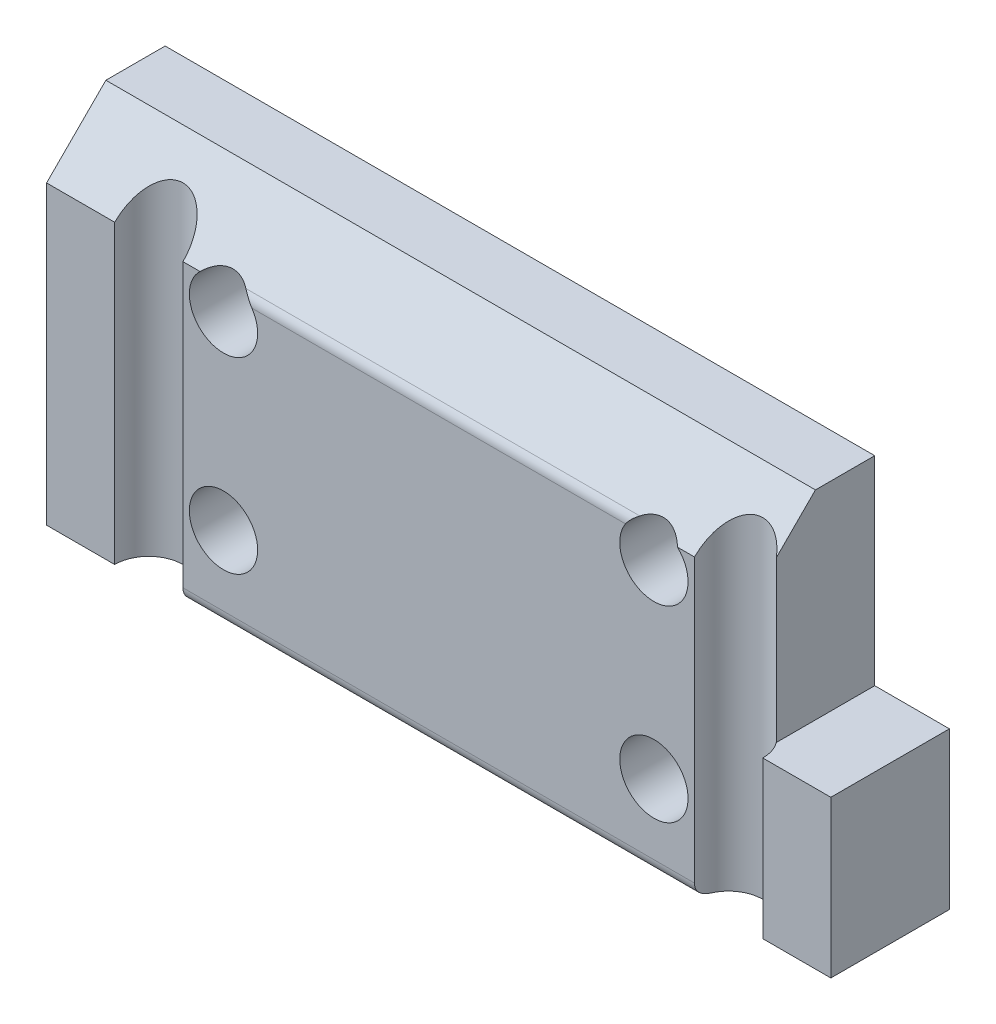
SolidWorks part; units mm, degrees
material "6061-T6 (SS)"
ref_plane "Front" through (0, 0, 0) normal (0, 0, 1) x (1, 0, 0)
ref_plane "Top" through (0, 0, 0) normal (0, 1, 0) x (1, 0, 0)
ref_plane "Right" through (0, 0, 0) normal (1, 0, 0) x (0, 0, -1)
ref_axis "side-side" through (80.9, 0, 0) along (-1, 0, 0)
ref_axis "up-down" through (0, 50, 0) along (0, -1, 0)
ref_axis "front-back" through (0, 0, -80.9) along (0, 0, 1)
sketch "Sketch1" plane through (0, 0, 0) normal (1, 0, 0) x (0, 0, -1)
  line L0 (0, 6.35) -> (3.175, 9.525)
  line L1 (3.175, 9.525) -> (6.35, 9.525)
  line L2 (0, 6.35) -> (0, -9.525)
  line L3 (0, -9.525) -> (6.35, -9.525)
  line L4 (6.35, 9.525) -> (6.35, -9.525)
  point P0 (6.35, 0)
  dimension "D1" = 6.35
  dimension "D2" = 19.05
  dimension "D3" = 45
  dimension "D4" = 3.175
extrude "Boss-Extrude1" add sketch "Sketch1" along normal mid plane 42
hole_wizard "CBORE for #6 Socket Head Cap Screw1" positions "Sketch3" profile "Sketch5" counterbore size "#6" standard "ANSI Inch"
sketch "Sketch3" plane through (0, 0, -6.35) normal (0, 0, -1) x (-1, 0, 0)
  line L0 (-9.525, 9.525) -> (-9.525, -9.525) construction
  line L1 (-21, 9.525) -> (21, 9.525) construction
  line L2 (-21, -9.525) -> (21, -9.525) construction
  line L3 (0, 0) -> (0, 16.0303) construction
  point P7 (-11.525, 5.025)
  point P9 (-11.525, -5.025)
  point P11 (11.525, 5.025)
  point P13 (11.525, -5.025)
  dimension "D1" = 9.525
  dimension "D2" = 4.5
  dimension "D3" = 4.5
  dimension "D4" = 2
  dimension "D5" = 23.05
sketch "Sketch5" plane through (-11.525, -5.025, -6.35) normal (1, 0, 0) x (0, 1, 0)
  line L0 (0, 0) -> (0, 10.4969)
  line L1 (0, 10.4969) -> (1.8288, 9.398)
  line L2 (1.8288, 9.398) -> (1.8288, 2.54)
  line L3 (1.8288, 2.54) -> (3.5725, 2.54)
  line L4 (3.5725, 2.54) -> (3.5725, 0)
  line L5 (3.5725, 0) -> (0, 0)
  line L10 (0, 10.4969) -> (-1.8288, 9.398) construction
  line L11 (0, -6.35) -> (0, 107.95) construction
  dimension "Hole Dia." = 3.6576
  dimension "Hole Depth" = 9.398
  dimension "C'Bore Dia." = 7.145
  dimension "C'Bore Depth" = 2.54
  dimension "Drill Angle" = 118
hole_wizard "#6 Clearance Hole1" positions "Sketch6" profile "Sketch7" hole size "#6" standard "ANSI Inch" end condition through all
sketch "Sketch6" plane through (0, -9.525, 0) normal (0, -1, 0) x (-1, 0, 0)
  line L0 (-21, 0) -> (21, 0) construction
  line L2 (0, 0) -> (0, 28.1383) construction
  line L3 (-21, 0) -> (-21, 6.35) construction
  point P0 (-15.525, 0)
  point P7 (15.525, 0)
  dimension "D1" = 4
  dimension "D2" = 5.475
  dimension "D3" = 31.05
  dimension "D4" = 6
sketch "Sketch7" plane through (15.525, -9.525, 0) normal (1, 0, 0) x (0, 0, -1)
  line L0 (0, 0) -> (0, 19.05)
  line L1 (0, 19.05) -> (1.8288, 19.05)
  line L2 (1.8288, 19.05) -> (1.8288, 0)
  line L5 (1.8288, 0) -> (0, 0)
  line L11 (0, -6.35) -> (0, 107.95) construction
  dimension "Thru Hole Dia." = 3.6576
  dimension "Thru Hole Depth" = 19.05
fillet "Fillet1" radius 0.75 2 edges at (0, 6.35, 0) (0, -9.525, 0)
sketch "Sketch8" plane through (0, 0, -6.35) normal (0, 0, -1) x (-1, 0, 0)
  line L1 (-21, 9.525) -> (-17, 9.525)
  line L2 (-21, 9.525) -> (-21, -1.143)
  line L3 (-21, -1.143) -> (-17, -1.143)
  line L4 (-17, 9.525) -> (-17, -1.143)
  dimension "D1" = 10.668
  dimension "D2" = 4
extrude "Cut-Extrude1" cut sketch "Sketch8" against normal through all
